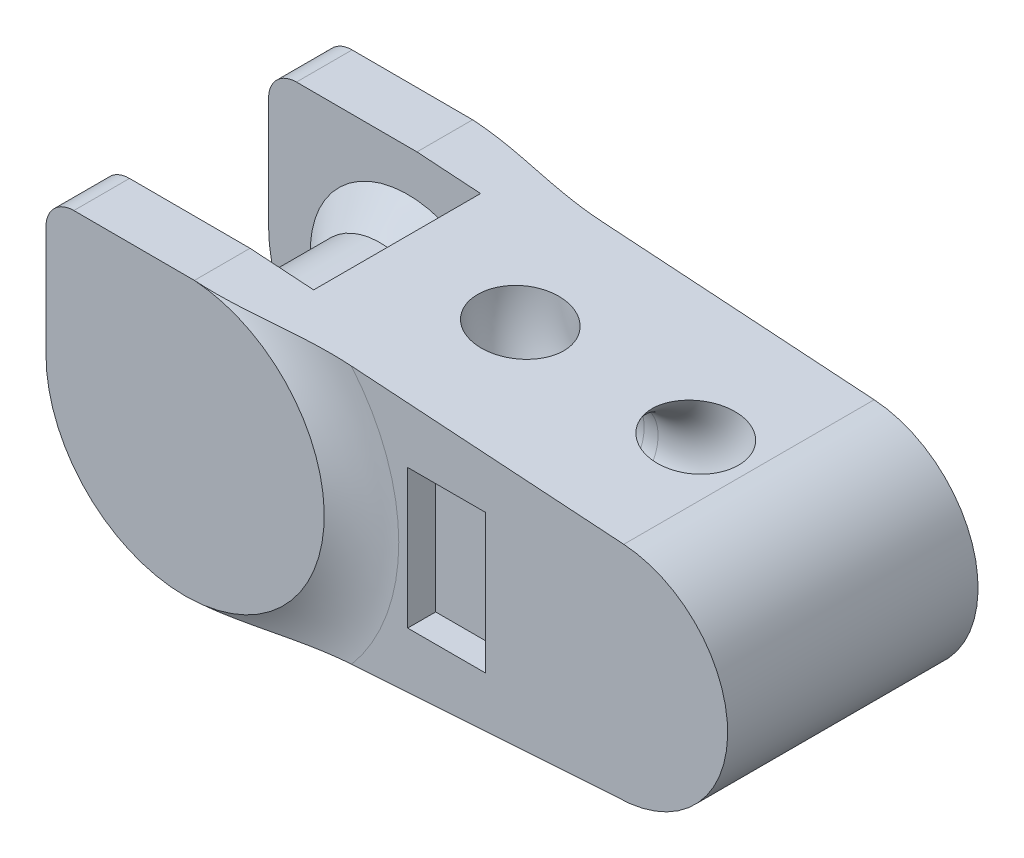
SolidWorks part; units mm, degrees
ref_plane "Front Plane" through (0, 0, 0) normal (0, 0, 1) x (1, 0, 0)
ref_plane "Top Plane" through (0, 0, 0) normal (0, 1, 0) x (1, 0, 0)
ref_plane "Right Plane" through (0, 0, 0) normal (1, 0, 0) x (0, 0, -1)
sketch "Sketch1" plane through (0, 0, 0) normal (0, 0, 1) x (1, 0, 0)
  line L0 (55, 0) -> (-55, 0) construction
  line L1 (0, -55) -> (0, 55) construction
  line L2 (-7.1667, 4.9889) -> (7.7667, 3.9911)
  line L3 (-7.5, -5) -> (7.5, -4)
  line L4 (-12.5, 0) -> (-12.5, 3.9979)
  line L5 (-11.4979, 4.9979) -> (-7.1667, 4.9889)
  arc A0 (-12.5, 0) -> (-7.8125, 4.9902) centre (-7.5, 0) ccw
  arc A1 (7.5, -4) -> (7.7667, 3.9911) centre (7.5, 0) ccw
  circle A2 centre (-7.5, 0) radius 2.5
  arc A3 (-12.5, 3.9979) -> (-11.4979, 4.9979) centre (-11.5, 3.9979) cw
  dimension "D1" = 10
  dimension "D2" = 8
  dimension "D5" = 5
  dimension "D6" = 1
  dimension "D3" = 15
  dimension "D4" = 7.5
extrude "Boss-Extrude1" add sketch "Sketch1" along normal mid plane 4 contours A1 L2 A0 L3 region at (3.3449, 0.0054, 0)
extrude "Boss-Extrude2" add sketch "Sketch1<3>" along normal mid plane 10 contours A0 L3 A2 region at (-2.6441, 0.1613, 0)
sketch "Sketch1<3>" plane through (0, 0, 0) normal (0, 0, 1) x (1, 0, 0) same geometry as "Sketch1"
extrude "Boss-Extrude3" add sketch "Sketch1<5>" along normal mid plane 9 contours A1 region at (3.3449, 0.0054, 0)
sketch "Sketch1<5>" plane through (0, 0, 0) normal (0, 0, 1) x (1, 0, 0) same geometry as "Sketch1"
fillet "Fillet1" radius 5 2 edges at (-2.5028, 0.166, 4.5) (-2.5028, 0.166, -4.5)
sketch "Sketch2" plane through (0, 0, 0) normal (0, 0, 1) x (1, 0, 0)
  line L0 (-2, 0) -> (-2, -5.5)
  line L1 (-2, -5.5) -> (-7.5, -5.5)
  line L2 (-13, 0) -> (-13, 5.518)
  line L3 (-13, 5.518) -> (-7.5, 5.5)
  arc A0 (-2, 0) -> (-7.5, 5.5) centre (-7.5, 0) ccw
  arc A1 (-13, 0) -> (-7.5, -5.5) centre (-7.5, 0) ccw
  dimension "D1" = 11
extrude "Cut-Extrude3" cut sketch "Sketch2" against normal mid plane 6 contours L0 A0 L1 region at (-7.5017, 0.0025, 0)
sketch "Sketch3" plane through (0, 0, 0) normal (0, 0, 1) x (1, 0, 0)
  line L0 (0, -6.5604) -> (0, 6.5604) construction
  line L2 (2.5, 2) -> (3, 2)
  line L9 (9.3408, 0) -> (-9.3408, 0) construction
  arc A2 (6, 5) -> (3, 2) centre (3, 5) cw
  arc A3 (2.5, 2) -> (-0.5, 5) centre (2.5, 5) cw
  point P24 (6.5, 2)
  point P27 (-1.5, 2)
  dimension "D1" = 6.5
  dimension "D2" = 0.5
  dimension "D3" = 2
sweep "Cut-Sweep5" cut path "Sketch3" circular profile diameter 3 parameters "D3"=3
mirror "Mirror4" about plane through (0, 0, 0) normal (0, 1, 0) of "Cut-Sweep5"
extrude "Boss-Extrude4" add sketch "Sketch1<7>" along normal mid plane 10 contours A2 region at (-7.5, 0, 0)
sketch "Sketch1<7>" plane through (0, 0, 0) normal (0, 0, 1) x (1, 0, 0) same geometry as "Sketch1"
chamfer "Chamfer2" distance 1 angle 45 2 edges at (-5, 0, -3) (-5, 0, 3)
sketch "Sketch16" plane through (0, 0, 0) normal (0, 1, 0) x (1, 0, 0)
  line L0 (7.7667, 4.5) -> (2.7878, 4.5)
  line L1 (-2.026, 4.5) -> (7.7667, 4.5) construction
  line L2 (2.7878, 4.5) -> (1.7878, 3.4953)
  line L3 (1.7878, 3.4953) -> (0, 3.4953)
  line L4 (0, -55) -> (0, 55) construction
  line L5 (0, 3.4953) -> (0, 4.5)
  line L6 (0, 4.5) -> (0, 5.995)
  line L7 (0, 5.995) -> (7.7193, 5.995)
  line L8 (7.7193, 5.995) -> (7.7667, 4.5)
  dimension "D1" = 1.0047
  dimension "D2" = 1
extrude "Cut-Extrude4" cut sketch "Sketch16" against normal mid plane 5
mirror "Mirror5" about plane through (0, 0, 0) normal (0, 0, 1) of "Cut-Extrude4"
